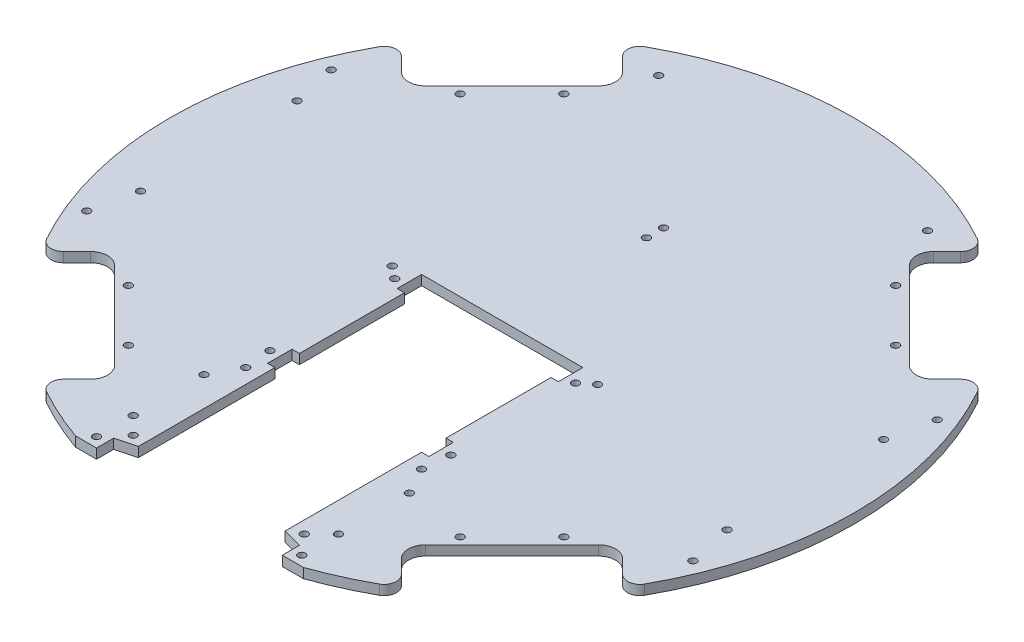
SolidWorks part; units mm, degrees
material "1060 Alloy"
ref_plane "Front Plane" through (0, 0, 0) normal (0, 0, 1) x (1, 0, 0)
ref_plane "Top Plane" through (0, 0, 0) normal (0, 1, 0) x (1, 0, 0)
ref_plane "Right Plane" through (0, 0, 0) normal (1, 0, 0) x (0, 0, -1)
sketch "Sketch1" plane through (0, 0, 0) normal (0, 1, 0) x (1, 0, 0)
  circle A0 centre (0, 0) radius 140
  dimension "D1" = 280
extrude "Boss-Extrude1" add sketch "Sketch1" along normal blind 4
sketch "Sketch7" plane through (0, 4, 0) normal (0, 1, 0) x (1, 0, 0)
  line L0 (-99.0303, -63.6043) -> (-63.6043, -99.0303)
  line L1 (-108.8591, -63.6043) -> (-121.6224, -76.3675)
  line L2 (-63.6043, -108.8591) -> (-76.3675, -121.6224)
  line L3 (-121.6224, -76.3675) -> (-76.3675, -121.6224)
  line L4 (0, 0) -> (-98.9949, -98.9949) construction
  line L7 (0, 0) -> (0, 130) construction
  circle A0 centre (0, 0) radius 140 construction
  arc A1 (-108.8591, -63.6043) -> (-99.0303, -63.6043) centre (-103.9447, -68.5186) cw
  arc A2 (-63.6043, -99.0303) -> (-63.6043, -108.8591) centre (-68.5186, -103.9447) cw
  dimension "D4" = 6.95
  dimension "D1" = 115
  dimension "D2" = 64
  dimension "D3" = 135
extrude "Cut-Extrude4" cut sketch "Sketch7" against normal up to next
sketch "Sketch9" plane through (0, 4, 0) normal (0, 1, 0) x (1, 0, 0)
  line L1 (-63.6043, -99.0303) -> (-99.0303, -63.6043) construction
  line L4 (-108.8591, -63.6043) -> (-119.0017, -73.7469) construction
  circle A0 centre (-89.0955, -67.8823) radius 1.5
  circle A1 centre (-67.8823, -89.0955) radius 1.5
  dimension "D4" = 3
  dimension "D1" = 4
  dimension "D2" = 30
  dimension "D3" = 17
  dimension "D5" = 4
extrude "Cut-Extrude6" cut sketch "Sketch9" against normal up to next
fillet "Fillet1" radius 5 2 edges at (-73.7469, 2, 119.0017) (-119.0017, 2, 73.7469)
pattern_circular "CirPattern1" count 4 over 360 about axis through (0, 4, 0) along (0, 1, 0) of "Cut-Extrude4", "Fillet1", "Cut-Extrude6"
sketch "Sketch2" plane through (0, 4, 0) normal (0, 1, 0) x (1, 0, 0)
  line L0 (-46.6476, -132) -> (-38, -132)
  line L1 (-30, -122.8564) -> (-30, -67)
  line L2 (-33, -4) -> (33, -4)
  line L3 (30, -67) -> (30, -122.8564)
  line L4 (38, -132) -> (46.6476, -132)
  line L5 (46.6476, -132) -> (46.6476, -140)
  line L6 (46.6476, -140) -> (-46.6476, -140)
  line L7 (-46.6476, -140) -> (-46.6476, -132)
  line L8 (-33, -57) -> (-33, -67)
  line L9 (-33, -67) -> (-30, -67)
  line L10 (33, -57) -> (33, -67)
  line L11 (33, -67) -> (30, -67)
  line L12 (-33, -57) -> (-30, -57)
  line L13 (-30, -57) -> (-30, -14)
  line L14 (-30, -14) -> (-33, -14)
  line L15 (-33, -14) -> (-33, -4)
  line L16 (33, -4) -> (33, -14)
  line L17 (33, -14) -> (30, -14)
  line L18 (30, -14) -> (30, -57)
  line L19 (30, -57) -> (33, -57)
  line L20 (-38, -132) -> (-38, -125)
  line L21 (-38, -125) -> (-30, -122.8564)
  line L22 (38, -132) -> (38, -125)
  line L23 (38, -125) -> (30, -122.8564)
  circle A0 centre (0, 0) radius 140 construction
  dimension "D8" = 3
  dimension "D5" = 63
  dimension "D6" = 66
  dimension "D1" = 8
  dimension "D2" = 65
  dimension "D3" = 60
  dimension "D4" = 16.6476
  dimension "D7" = 10
  dimension "D9" = 76
  dimension "D10" = 7
  dimension "D11" = 105
extrude "Cut-Extrude1" cut sketch "Sketch2" against normal up to next
fillet "Fillet3" radius 1.5 8 edges at (67.8823, 0, 90.5955) (89.0955, 0, 69.3823) (89.0955, 0, -66.3823) (67.8823, 0, -87.5955) (-67.8823, 0, -87.5955) (-89.0955, 0, -66.3823) (-67.8823, 0, 90.5955) (-89.0955, 0, 69.3823)
sketch "Sketch10" plane through (0, 4, 0) normal (0, 1, 0) x (1, 0, 0)
  line L0 (-33, -57) -> (-33, -67) construction
  line L1 (33, -67) -> (33, -57) construction
  line L2 (-33, -67) -> (-30, -67) construction
  line L4 (-30, -14) -> (-33, -14) construction
  line L5 (33, -4) -> (-33, -4) construction
  circle A0 centre (-37, -62) radius 1.5
  circle A1 centre (37, -62) radius 1.5
  circle A2 centre (-37, -11) radius 1.5
  circle A3 centre (37, -11) radius 1.5
  circle A4 centre (-42, -7) radius 1.5
  circle A5 centre (42, -7) radius 1.5
  point P17 (-31.5, -14)
  dimension "D3" = 3
  dimension "D1" = 4
  dimension "D2" = 4
  dimension "D4" = 5
  dimension "D5" = 3
  dimension "D6" = 3
  dimension "D7" = 5
  dimension "D8" = 5
extrude "Cut-Extrude7" cut sketch "Sketch10" against normal up to next
sketch "Sketch13" plane through (0, 4, 0) normal (0, 1, 0) x (1, 0, 0)
  line L0 (-38, -132) -> (-46.6476, -132) construction
  line L1 (-38, -132) -> (-46.6476, -132) construction
  circle A0 centre (-42, -84) radius 1.5
  circle A1 centre (-42, -113) radius 1.5
  circle A2 centre (42, -113) radius 1.5
  circle A3 centre (42, -84) radius 1.5
  dimension "D1" = 3
  dimension "D2" = 19
  dimension "D3" = 48
  dimension "D4" = 42
  dimension "D5" = 42
extrude "Cut-Extrude9" cut sketch "Sketch13" against normal up to next
sketch "Sketch16" plane through (0, 4, 0) normal (0, 1, 0) x (1, 0, 0)
  circle A0 centre (0, 62) radius 1.5
  circle A4 centre (0, 55) radius 1.5
  dimension "D2" = 3
  dimension "D5" = 3
  dimension "D1" = 62
  dimension "D7" = 55
extrude "Cut-Extrude12" cut sketch "Sketch16" against normal up to next
sketch "Sketch17" plane through (0, 4, 0) normal (0, 1, 0) x (1, 0, 0)
  circle A0 centre (-124, 50) radius 1.5
  circle A1 centre (-124, -50) radius 1.5
  circle A2 centre (124, 50) radius 1.5
  circle A3 centre (124, -50) radius 1.5
  dimension "D1" = 3
  dimension "D2" = 50
  dimension "D3" = 50
  dimension "D4" = 124
  dimension "D5" = 124
extrude "Cut-Extrude13" cut sketch "Sketch17" against normal up to next
sketch "Sketch18" plane through (0, 4, 0) normal (0, 1, 0) x (1, 0, 0)
  line L1 (-27, -4) -> (27, -4)
  line L2 (-27, -4) -> (-27, 46)
  line L3 (-27, 46) -> (27, 46)
  line L4 (27, -4) -> (27, 46)
  line L5 (33, -4) -> (-33, -4) construction
  dimension "D1" = 50
  dimension "D2" = 54
  dimension "D3" = 27
extrude "Cut-Extrude14" [suppressed] cut sketch "Sketch18" against normal blind 0.8
sketch "Sketch19" plane through (0, 4, 0) normal (0, 1, 0) x (1, 0, 0)
  line L0 (-38, -125) -> (-38, -132) construction
  line L1 (-38, -132) -> (-46.6476, -132) construction
  line L2 (38, -132) -> (38, -125) construction
  circle A0 centre (-42, -128) radius 1.5
  circle A1 centre (42, -128) radius 1.5
  dimension "D4" = 3
  dimension "D1" = 4
  dimension "D2" = 4
  dimension "D3" = 4
extrude "Cut-Extrude15" cut sketch "Sketch19" against normal up to next
sketch "Sketch20" [suppressed] plane through (0, 3, 0) normal (0, 1, 0) x (1, 0, 0)
  line L0 (27, 46) -> (-27, 46) construction
  line L1 (-6, 46) -> (6, 46)
  line L2 (-6, 46) -> (-6, 52)
  line L3 (-6, 52) -> (6, 52)
  line L4 (6, 46) -> (6, 52)
  circle A0 centre (0, 55) radius 1.5 construction
  dimension "D1" = 12
  dimension "D2" = 6
  dimension "D3" = 3
extrude "Cut-Extrude16" [suppressed] cut sketch "Sketch20" against normal up to surface (0.8 mm away) up to face at (42, 4, 129.5)
fillet "Fillet4" [suppressed] radius 1.5
sketch "Sketch21" plane through (0, 4, 0) normal (0, 1, 0) x (1, 0, 0)
  circle A0 centre (-35, -120) radius 1.5
  circle A1 centre (-36, -73) radius 1.5
  circle A2 centre (35, -120) radius 1.5
  circle A3 centre (36, -73) radius 1.5
  circle A4 centre (-42, -128) radius 1.5 construction
  circle A5 centre (42, -128) radius 1.5 construction
  dimension "D1" = 7
  dimension "D3" = 3
  dimension "D2" = 8
  dimension "D4" = 47
  dimension "D5" = 1
  dimension "D6" = 1
  dimension "D7" = 7
extrude "Cut-Extrude17" cut sketch "Sketch21" against normal up to next
sketch "Sketch22" plane through (0, 4, 0) normal (0, 1, 0) x (1, 0, 0)
  circle A0 centre (120, 32) radius 1.5
  circle A1 centre (120, -32) radius 1.5
  circle A2 centre (-120, 32) radius 1.5
  circle A3 centre (-120, -32) radius 1.5
  dimension "D1" = 3
  dimension "D2" = 120
  dimension "D3" = 32
  dimension "D4" = 32
  dimension "D5" = 120
extrude "Cut-Extrude18" cut sketch "Sketch22" against normal up to next
sketch "Sketch23" plane through (0, 4, 0) normal (0, 1, 0) x (1, 0, 0)
  circle A0 centre (-55, 115) radius 1.5
  circle A1 centre (55, 115) radius 1.5
  dimension "D1" = 3
  dimension "D2" = 55
  dimension "D3" = 115
  dimension "D4" = 55
extrude "Cut-Extrude19" cut sketch "Sketch23" against normal up to next
